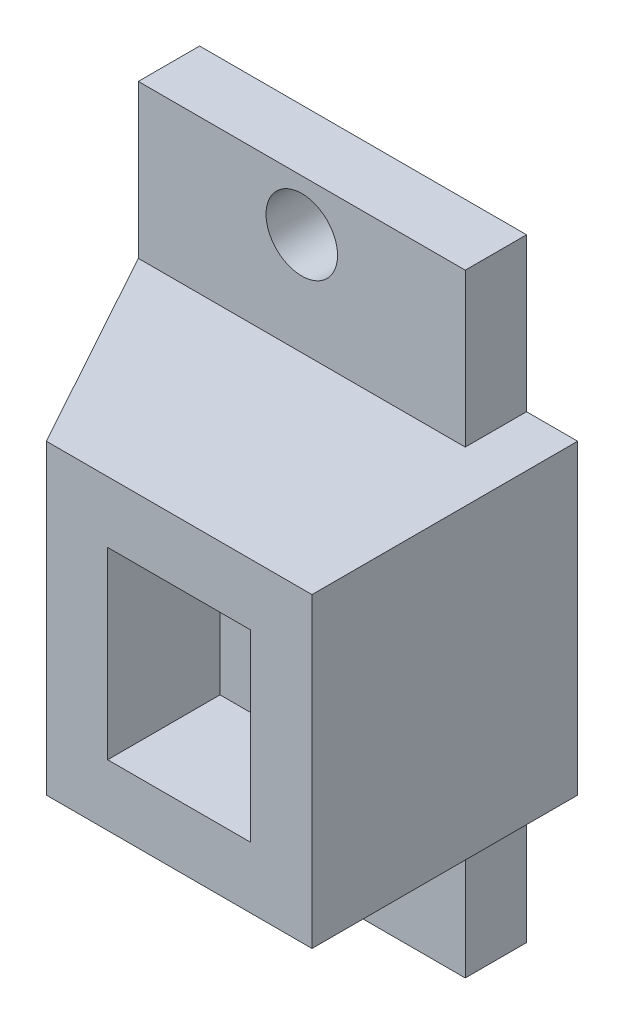
SolidWorks part; units mm, degrees
ref_plane "Plan de face" through (0, 0, 0) normal (0, 0, 1) x (1, 0, 0)
ref_plane "Plan de dessus" through (0, 0, 0) normal (0, 1, 0) x (1, 0, 0)
ref_plane "Plan de droite" through (0, 0, 0) normal (1, 0, 0) x (0, 0, -1)
sketch "Esquisse1" plane through (0, 0, 0) normal (0, 0, 1) x (1, 0, 0)
  line L0 (-6.5, 7.5) -> (-6.5, -7.5)
  line L1 (-3.5, 4.5) -> (3.5, 4.5)
  line L2 (-3.5, 4.5) -> (-3.5, -4.5)
  line L3 (-3.5, -4.5) -> (3.5, -4.5)
  line L4 (3.5, 4.5) -> (3.5, -4.5)
  line L5 (-6.5, -7.5) -> (6.5, -7.5)
  line L6 (6.5, 7.5) -> (6.5, -7.5)
  line L7 (-6.5, 7.5) -> (6.5, 7.5)
  line L12 (-9.25, 0) -> (-12, 0) construction
  line L13 (-12, 10) -> (12, 10)
  line L14 (-12, 10) -> (-12, -10)
  line L15 (-12, -10) -> (12, -10)
  line L16 (12, 10) -> (12, -10)
  line L17 (-9.25, 0) -> (-6.5, 0) construction
  line L18 (9.25, 0) -> (6.5, 0) construction
  line L19 (9.25, 0) -> (12, 0) construction
  line L20 (4, -10) -> (4, -15)
  line L21 (4, -15) -> (-12, -15)
  line L22 (-12, -15) -> (-12, -10)
  line L23 (-12, 15) -> (-12, 10)
  line L24 (4, 15) -> (-12, 15)
  line L25 (4, 10) -> (4, 15)
  line L26 (4, -10) -> (4, -7.5)
  line L27 (4, 7.5) -> (4, 10)
  circle A0 centre (-9.25, 0) radius 1.75
  circle A1 centre (9.25, 0) radius 1.75
  circle A2 centre (-4, -12.5) radius 1.75
  circle A3 centre (-4, 12.5) radius 1.75
  point P8 (0, 4.5)
  point P10 (-3.5, 0)
  point P15 (-12, 0)
  point P16 (0, -10)
  point P31 (-12, -12.5)
  point P32 (-4, -15)
  dimension "D5" = 20
  dimension "D6" = 3.5
  dimension "D1" = 3
  dimension "D2" = 7
  dimension "D3" = 9
  dimension "D4" = 24
  dimension "D7" = 16
  dimension "D8" = 5
extrude "Boss.-Extru.1" add sketch "Esquisse1" along normal blind 3 contours L13 L15 L0 L7 L6 L5 | L22 L21 L20 L15 A2 | L13 L25 L24 L23 A3 region at (-6.5027, 0, 0) region at (-4, 10.1676, 0) region at (3.8324, -12.5, 0)
extrude "Boss.-Extru.2" add sketch "Esquisse1<3>" along normal blind 13 contours L7 L0 L5 L6 L1 L4 L3 L2 region at (-1.25, 7.3015, 0)
sketch "Esquisse1<3>" plane through (0, 0, 0) normal (0, 0, 1) x (1, 0, 0) same geometry as "Esquisse1"
sketch "Esquisse5" plane through (0, -7.5, 0) normal (0, -1, 0) x (1, 0, 0)
  line L0 (-6.5, 13) -> (-12, 3)
  line L1 (-12, 3) -> (-12, 0) construction
  line L2 (4, 3) -> (-12, 3) construction
rib "Nervure2" sketch "Esquisse5" sketch "Esquisse5" thickness 3 extrusion direction parallel to sketch draft on no parameters "D1"=3
mirror "Symétrie4" about plane through (0, 0, 0) normal (0, 1, 0) of "Nervure2"
extrude "Boss.-Extru.3" add sketch "Esquisse1<4>" along normal blind 7.5 contours L4 L1 L2 L3 region at (0, 0, 0)
sketch "Esquisse1<4>" plane through (0, 0, 0) normal (0, 0, 1) x (1, 0, 0) same geometry as "Esquisse1"
